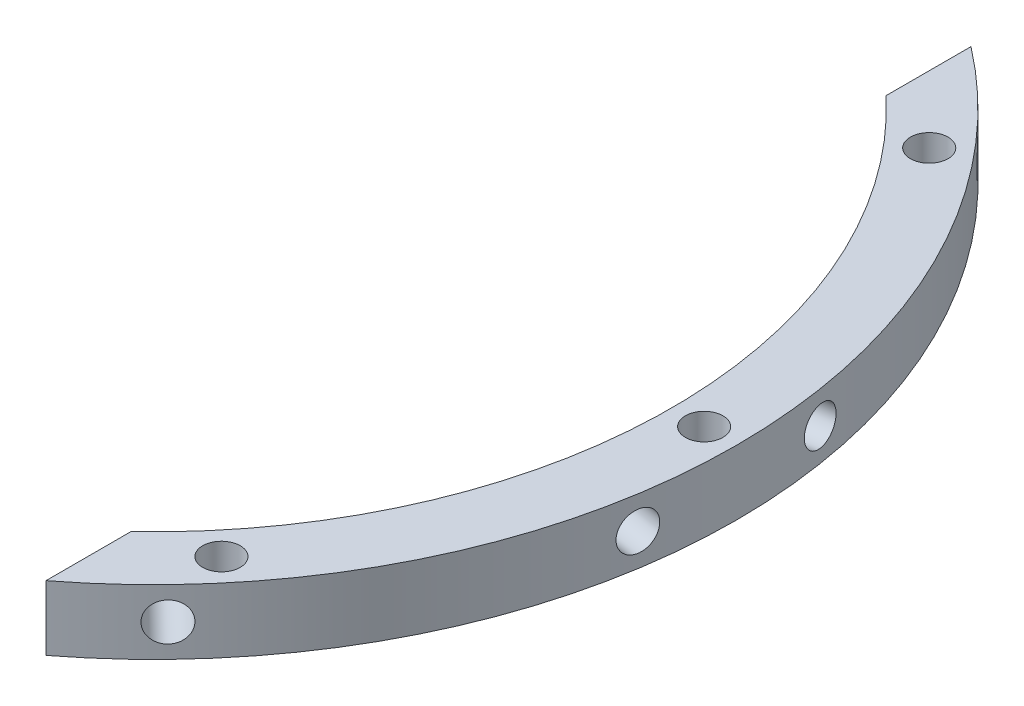
SolidWorks part; units mm, degrees
ref_plane "Спереди" through (0, 0, 0) normal (0, 0, 1) x (1, 0, 0)
ref_plane "Сверху" through (0, 0, 0) normal (0, 1, 0) x (1, 0, 0)
ref_plane "Справа" through (0, 0, 0) normal (1, 0, 0) x (0, 0, -1)
sketch "Эскиз1" plane through (0, 0, 0) normal (0, 1, 0) x (1, 0, 0)
  line L0 (27.3954, 29.146) -> (27.3954, 35.7)
  line L1 (27.3954, -35.7) -> (27.3954, -29.146)
  arc A0 (27.3954, 35.7) -> (27.3954, -35.7) centre (0, 0) cw
  arc A1 (27.3954, 29.146) -> (27.3954, -29.146) centre (0, 0) cw
  dimension "D3" = 45
  dimension "D2" = 5
  dimension "D1" = 71.4
extrude "Бобышка-Вытянуть1" add sketch "Эскиз1" along normal blind 5
sketch "Эскиз2" plane through (0, 5, 0) normal (0, 1, 0) x (1, 0, 0)
  line L0 (-1000, 0) -> (49000, 0) construction
  line L1 (0, 0) -> (32.5569, 27.3185) construction
  circle A0 centre (0, 0) radius 42.5 construction
  circle A1 centre (42.5, 0) radius 1.45
  circle A2 centre (32.5569, 27.3185) radius 1.45
  circle A4 centre (32.5569, -27.3185) radius 1.45
  dimension "D1" = 85
  dimension "D2" = 40
  dimension "D3" = 2.9
extrude "Вырез-Вытянуть1" cut sketch "Эскиз2" against normal blind 5
ref_axis "Ось1" through (0, -0.25, 0) along (0, 1, 0)
ref_plane "Плоскость4" through (0, 0, 0) normal (0.7193, 0, 0.6947) x (0, 1, 0)
sketch "Эскиз3" plane through (0, 0, 0) normal (0.7193, 0, 0.6947) x (0, 1, 0)
  line L1 (-0.25, 0) -> (5.25, 0) construction
  line L2 (0, 6.65) -> (0, -45) construction
  circle A0 centre (2.5, 0) radius 1.475
  dimension "D1" = 2.95
  dimension "D2" = 2.5
extrude "Вырез-Вытянуть2" cut sketch "Эскиз3" along normal blind 46
pattern_circular "Круговой массив1" count 2 every 35 about axis through (0, -0.25, 0) along (0, 1, 0) of "Вырез-Вытянуть2"
mirror "Зеркальное отражение1" about plane through (0, 0, 0) normal (0, 0, 1) of "Вырез-Вытянуть2", "Круговой массив1"
